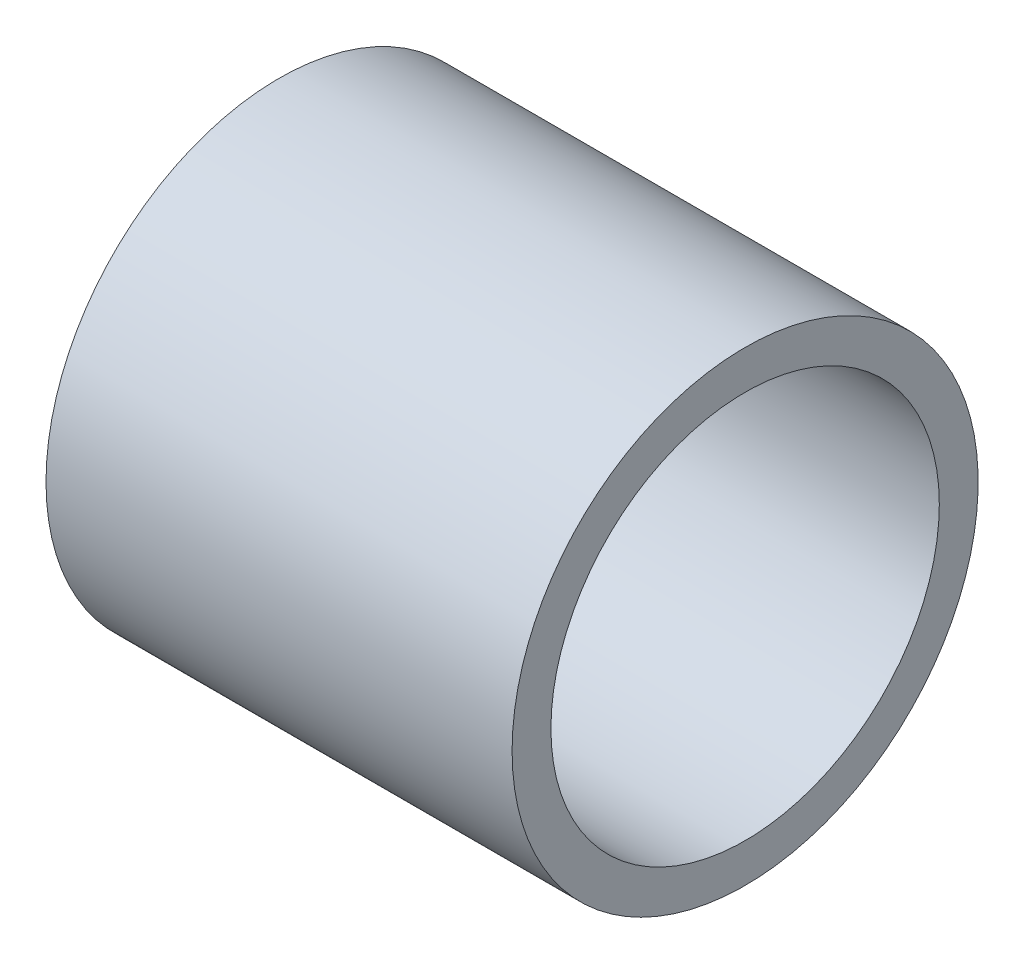
SolidWorks part; units mm, degrees
material "7075-O (SS)"
ref_plane "Front Plane" through (0, 0, 0) normal (0, 0, 1) x (1, 0, 0)
ref_plane "Top Plane" through (0, 0, 0) normal (0, 1, 0) x (1, 0, 0)
ref_plane "Right Plane" through (0, 0, 0) normal (1, 0, 0) x (0, 0, -1)
sketch "Sketch1" plane through (0, 0, 0) normal (1, 0, 0) x (0, 0, -1)
  circle A0 centre (0, 0) radius 1.5875
  circle A1 centre (0, 0) radius 1.905
  dimension "D1" = 3.175
  dimension "D2" = 0.3175
extrude "Boss-Extrude1" add sketch "Sketch1" along normal blind 3.81
ref_axis "Axis1" through (3.81, 0, 0) along (-1, 0, 0)
